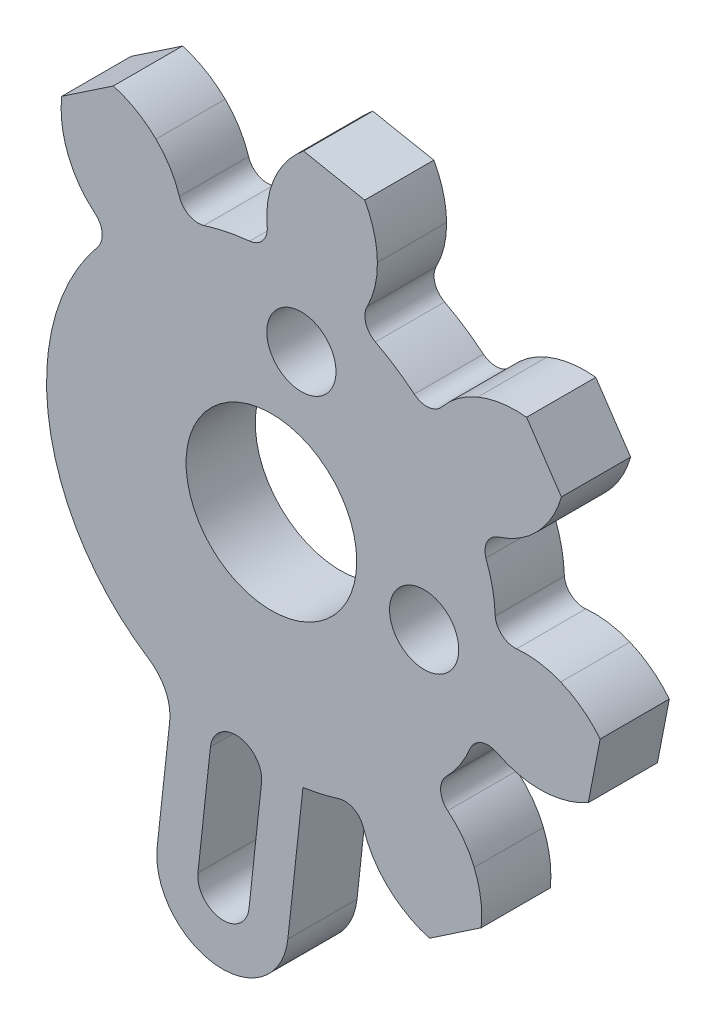
SolidWorks part; units mm, degrees
ref_plane "Plan de face" through (0, 0, 0) normal (0, 0, 1) x (1, 0, 0)
ref_plane "Plan de dessus" through (0, 0, 0) normal (0, 1, 0) x (1, 0, 0)
ref_plane "Plan de droite" through (0, 0, 0) normal (1, 0, 0) x (0, 0, -1)
sketch "Esquisse1" plane through (0, 0, 0) normal (0, 0, 1) x (1, 0, 0)
  line L0 (1344.4447, 1938.2222) -> (1339.1234, 1905.8567) construction
  line L1 (1343.247, 1938.3023) -> (1345.8975, 1937.7875)
  line L2 (1344.5722, 1938.0449) -> (1343.7125, 1933.619) construction
  line L3 (1352.9182, 1933.1417) -> (1354.4282, 1930.9035)
  line L4 (1356.1076, 1922.6541) -> (1355.5927, 1920.0037)
  line L5 (1350.947, 1912.983) -> (1348.7088, 1911.4729)
  line L6 (1343.2216, 1914.3944) -> (1342.5656, 1908.3681)
  line L7 (1337.4424, 1913.9768) -> (1336.8991, 1908.9848)
  line L8 (1340.8802, 1908.667) -> (1341.4251, 1913.6727)
  line L9 (1332.7594, 1935.1129) -> (1334.9976, 1936.623)
  line L10 (1340.4594, 1909.7935) -> (1337.8089, 1910.3084)
  line L11 (1330.7882, 1914.9541) -> (1329.2782, 1917.1923)
  line L12 (1327.5988, 1925.4417) -> (1328.1137, 1928.0922)
  line L13 (1339.211, 1913.9137) -> (1338.6662, 1908.908)
  circle A0 centre (1341.8532, 1924.0479) radius 3.7
  circle A1 centre (1341.8532, 1924.0479) radius 9.75 construction
  arc A2 (1343.247, 1938.3023) -> (1341.9613, 1936.593) centre (1345.9818, 1934.9072) ccw
  arc A3 (1341.9613, 1936.593) -> (1341.6715, 1934.6793) centre (1345.6154, 1935.0608) ccw
  arc A4 (1341.6715, 1934.6793) -> (1340.9083, 1933.752) centre (1340.826, 1934.5975) cw
  arc A5 (1346.0019, 1933.8381) -> (1346.3625, 1932.6925) centre (1346.7553, 1933.4457) ccw
  arc A6 (1346.4497, 1935.7211) -> (1346.0019, 1933.8381) centre (1342.4877, 1935.6684) cw
  arc A7 (1345.8975, 1937.7875) -> (1346.4497, 1935.7211) centre (1342.0904, 1935.6631) cw
  arc A8 (1351.7095, 1928.037) -> (1351.1544, 1926.972) centre (1351.9647, 1927.2268) ccw
  arc A9 (1353.3576, 1929.0519) -> (1351.7095, 1928.037) centre (1350.5188, 1931.8162) cw
  arc A10 (1354.4282, 1930.9035) -> (1353.3576, 1929.0519) centre (1350.2341, 1932.0933) cw
  arc A11 (1352.9182, 1933.1417) -> (1350.8004, 1932.8422) centre (1352.4512, 1928.8072) ccw
  arc A12 (1350.8004, 1932.8422) -> (1349.2422, 1931.6939) centre (1352.3008, 1929.1749) ccw
  arc A13 (1349.2422, 1931.6939) -> (1348.0469, 1931.5779) centre (1348.5865, 1932.2339) cw
  arc A14 (1351.6433, 1919.8992) -> (1350.4978, 1919.5387) centre (1351.2509, 1919.1458) ccw
  arc A15 (1353.5264, 1919.4515) -> (1351.6433, 1919.8992) centre (1353.4737, 1923.4134) cw
  arc A16 (1355.5927, 1920.0037) -> (1353.5264, 1919.4515) centre (1353.4684, 1923.8107) cw
  arc A17 (1356.1076, 1922.6541) -> (1354.3983, 1923.9398) centre (1352.7124, 1919.9193) ccw
  arc A18 (1354.3983, 1923.9398) -> (1352.4846, 1924.2296) centre (1352.8661, 1920.2857) ccw
  arc A19 (1352.4846, 1924.2296) -> (1351.5573, 1924.9928) centre (1352.4028, 1925.0751) cw
  arc A20 (1345.8423, 1914.1917) -> (1344.7773, 1914.7467) centre (1345.0321, 1913.9364) ccw
  arc A21 (1346.8572, 1912.5435) -> (1345.8423, 1914.1917) centre (1349.6215, 1915.3824) cw
  arc A22 (1348.7088, 1911.4729) -> (1346.8572, 1912.5435) centre (1349.8986, 1915.667) cw
  arc A23 (1350.947, 1912.983) -> (1350.6474, 1915.1007) centre (1346.6125, 1913.4499) ccw
  arc A24 (1350.6474, 1915.1007) -> (1349.4992, 1916.6589) centre (1346.9802, 1913.6003) ccw
  arc A25 (1349.4992, 1916.6589) -> (1349.3832, 1917.8542) centre (1350.0392, 1917.3146) cw
  arc A26 (1338.9291, 1933.3491) -> (1340.9083, 1933.752) centre (1341.8532, 1924.0479) cw
  arc A27 (1346.3625, 1932.6925) -> (1348.0469, 1931.5779) centre (1341.8532, 1924.0479) cw
  arc A28 (1351.1544, 1926.972) -> (1351.5573, 1924.9928) centre (1345.611, 1924.8129) cw
  arc A29 (1350.4978, 1919.5387) -> (1349.3832, 1917.8542) centre (1345.7506, 1921.469) cw
  arc A30 (1344.7773, 1914.7467) -> (1343.2216, 1914.3944) centre (1341.8532, 1924.0479) cw
  arc A31 (1342.5656, 1908.3681) -> (1336.8991, 1908.9848) centre (1339.7324, 1908.6765) cw
  arc A32 (1336.5434, 1915.8706) -> (1334.3232, 1930.2416) centre (1341.8532, 1924.0479) cw
  arc A33 (1337.4424, 1913.9768) -> (1336.5434, 1915.8706) centre (1335.4542, 1914.1932) ccw
  circle A34 centre (1343.153, 1930.7174) radius 1.5
  circle A35 centre (1348.476, 1922.9463) radius 1.5
  arc A36 (1338.6662, 1908.908) -> (1340.8802, 1908.667) centre (1339.7732, 1908.7875) ccw
  arc A38 (1339.211, 1913.9137) -> (1341.4251, 1913.6727) centre (1340.3181, 1913.7932) cw
  arc A44 (1337.8641, 1933.9042) -> (1338.9291, 1933.3491) centre (1338.6743, 1934.1595) ccw
  arc A45 (1336.8492, 1935.5523) -> (1337.8641, 1933.9042) centre (1334.0849, 1932.7135) cw
  arc A46 (1334.9976, 1936.623) -> (1336.8492, 1935.5523) centre (1333.8078, 1932.4288) cw
  arc A47 (1332.7594, 1935.1129) -> (1333.059, 1932.9951) centre (1337.0939, 1934.6459) ccw
  arc A48 (1333.059, 1932.9951) -> (1334.2072, 1931.437) centre (1336.7262, 1934.4955) ccw
  arc A49 (1334.2072, 1931.437) -> (1334.3232, 1930.2416) centre (1333.6672, 1930.7813) cw
  arc A50 (1342.0349, 1913.4166) -> (1342.7981, 1914.3438) centre (1342.8804, 1913.4984) cw
  arc A51 (1341.745, 1911.5028) -> (1342.0349, 1913.4166) centre (1338.091, 1913.0351) ccw
  arc A52 (1340.4594, 1909.7935) -> (1341.745, 1911.5028) centre (1337.7246, 1913.1887) ccw
  arc A53 (1337.8089, 1910.3084) -> (1337.2567, 1912.3747) centre (1341.616, 1912.4328) cw
  arc A54 (1337.2567, 1912.3747) -> (1337.7045, 1914.2578) centre (1341.2187, 1912.4275) cw
  arc A55 (1337.7045, 1914.2578) -> (1337.3439, 1915.4033) centre (1336.9511, 1914.6502) ccw
  arc A56 (1334.4642, 1916.402) -> (1335.6595, 1916.518) centre (1335.1199, 1915.8619) cw
  arc A57 (1332.906, 1915.2537) -> (1334.4642, 1916.402) centre (1331.4056, 1918.921) ccw
  arc A58 (1330.7882, 1914.9541) -> (1332.906, 1915.2537) centre (1331.2552, 1919.2887) ccw
  arc A59 (1329.2782, 1917.1923) -> (1330.3488, 1919.0439) centre (1333.4723, 1916.0025) cw
  arc A60 (1330.3488, 1919.0439) -> (1331.9969, 1920.0589) centre (1333.1876, 1916.2797) cw
  arc A61 (1331.9969, 1920.0589) -> (1332.552, 1921.1238) centre (1331.7417, 1920.8691) ccw
  arc A62 (1331.2218, 1923.8662) -> (1332.1491, 1923.1031) centre (1331.3036, 1923.0207) cw
  arc A63 (1327.5988, 1925.4417) -> (1329.3081, 1924.1561) centre (1330.994, 1928.1766) ccw
  arc A64 (1329.3081, 1924.1561) -> (1331.2218, 1923.8662) centre (1330.8403, 1927.8102) ccw
  arc A65 (1328.1137, 1928.0922) -> (1330.18, 1928.6444) centre (1330.238, 1924.2852) cw
  arc A66 (1330.18, 1928.6444) -> (1332.0631, 1928.1967) centre (1330.2327, 1924.6824) cw
  arc A67 (1332.0631, 1928.1967) -> (1333.2086, 1928.5572) centre (1332.4555, 1928.9501) ccw
  point P122 (1341.8532, 1924.0479)
  dimension "D2" = 7.4
  dimension "D3" = 19.5
  dimension "D4" = 2.7
  dimension "D6" = 5.7
  dimension "D7" = 2
  dimension "D8" = 3
  dimension "D9" = 3
  dimension "D1" = 32.8
  dimension "D5" = 8
base flange "Tôle de base pliée1" sketch "Esquisse1" thickness 3 reverse thickness direction no parameters "D1"=1.5
sketch "Lignes de pliage1" [suppressed] plane through (0, 0, 0) normal (0, 1, 0) x (1, 0, 0)
sketch "Cube de visualisation1" [suppressed] plane through (0, 0, 0) normal (0, 1, 0) x (1, 0, 0)
sheet metal parameters "Tôlerie1" thickness 3 parameters "D1"=1.5
flat pattern "Etat déplié1" [suppressed]
sketch "Lignes de pliage2" plane through (0, 0, 0) normal (0, 1, 0) x (1, 0, 0)
sketch3d "Cube de visualisation2" [suppressed]
  line L0 (6.5552, 5.2864, 0) -> (12.7749, -25.266, 0) construction
  line L1 (-16.4135, 0.6105, 0) -> (-10.1938, -29.9418, 0) construction
  line L2 (6.5552, 5.2864, 0) -> (-16.4135, 0.6105, 0) construction
  line L3 (12.7749, -25.266, 0) -> (-10.1938, -29.9418, 0) construction
